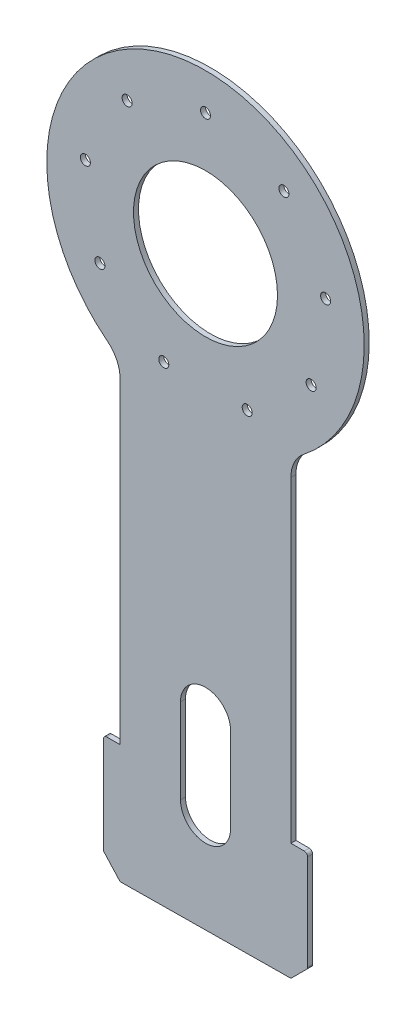
SolidWorks part; units mm, degrees
ref_plane "Front Plane" through (0, 0, 0) normal (0, 0, 1) x (1, 0, 0)
ref_plane "Top Plane" through (0, 0, 0) normal (0, 1, 0) x (1, 0, 0)
ref_plane "Right Plane" through (0, 0, 0) normal (1, 0, 0) x (0, 0, -1)
sketch "Sketch1" plane through (0, 0, 0) normal (0, 0, 1) x (1, 0, 0)
  circle A0 centre (0, 0) radius 47.5
  circle A1 centre (0, 0) radius 21.55
  dimension "D1" = 95
  dimension "D2" = 43.1
extrude "Boss-Extrude1" add sketch "Sketch1" along normal blind 1.5
sketch "Sketch2" plane through (0, 0, 1.5) normal (0, 0, 1) x (1, 0, 0)
  circle A0 centre (0, 0) radius 36.5 construction
  dimension "D1" = 73
sketch "Sketch3" plane through (0, 0, 1.5) normal (0, 0, 1) x (1, 0, 0)
  circle A0 centre (0, 36.5) radius 1.5
  circle A1 centre (0, 0) radius 36.5 construction
  point P0 (0, 36.5)
  dimension "D1" = 3
hole_wizard "Ø3.0mm Dowel Hole1" positions "Sketch3" profile "Sketch4" hole size "Ø3.0" standard "ANSI Metric" end condition through all
sketch "Sketch4" plane through (0, 36.5, 1.5) normal (1, 0, 0) x (0, -1, 0)
  line L0 (0, 0) -> (0, 1.5)
  line L1 (0, 1.5) -> (1.5, 1.5)
  line L2 (1.5, 1.5) -> (1.5, 0)
  line L5 (1.5, 0) -> (0, 0)
  line L11 (0, -6.35) -> (0, 107.95) construction
  dimension "Thru Hole Dia." = 3
  dimension "Thru Hole Depth" = 1.5
pattern_circular "CirPattern1" count 9 over 360 about axis through (0, 0, 1.5) along (0, 0, 1) of "Ø3.0mm Dowel Hole1"
sketch "Sketch6" plane through (0, 0, 1.5) normal (0, 0, 1) x (1, 0, 0)
  line L0 (0, -47.5) -> (0, -40.0345) construction
  line L1 (0, -40.0345) -> (-25.5634, -40.0345) construction
  line L2 (-25.5634, -40.0345) -> (25.5634, -40.0345) construction
  line L3 (-25.5634, -40.0345) -> (25.5634, -40.0345)
  line L4 (-25.5634, -40.0345) -> (-25.5634, -140.0345)
  line L5 (-25.5634, -140.0345) -> (-30.5634, -140.0345)
  line L6 (-30.5634, -140.0345) -> (-30.5634, -170.0345)
  line L7 (-30.5634, -170.0345) -> (-25.5634, -175.5368)
  line L8 (30.5634, -140.0345) -> (30.5634, -170.0345)
  line L9 (25.5634, -40.0345) -> (25.5634, -140.0345)
  line L10 (25.5634, -140.0345) -> (30.5634, -140.0345)
  line L11 (30.5634, -170.0345) -> (25.5634, -175.0345)
  line L12 (25.5634, -175.0345) -> (-25.5634, -175.5368)
  circle A1 centre (0, 0) radius 47.5 construction
extrude "Boss-Extrude2" add sketch "Sketch6" against normal blind 1.5
fillet "Fillet7" radius 10 1 edges at (-25.5634, -40.0345, 0.75)
fillet "Fillet8" radius 10 1 edges at (25.5634, -40.0345, 0.75)
fillet "Fillet9" radius 1 2 edges at (-30.5634, -140.0345, 0.75) (30.5634, -140.0345, 0.75)
fillet "Fillet10" radius 1 4 edges at (-30.5634, -170.0345, 0.75) (-25.5634, -175.5368, 0.75) (25.5634, -175.0345, 0.75) (30.5634, -170.0345, 0.75)
sketch "Sketch8" plane through (0, 0, 0) normal (0, 0, -1) x (-1, 0, 0)
  line L0 (-0.02, -175.2854) -> (-0.02, -145.2854) construction
  line L1 (25.1151, -175.5324) -> (-25.155, -175.0385) construction
  line L2 (-0.02, -145.2854) -> (-0.02, -119.8854) construction
  line L3 (-7.52, -145.2854) -> (-7.52, -119.8854)
  line L4 (7.48, -145.2854) -> (7.48, -119.8854)
  arc A0 (-7.52, -145.2854) -> (7.48, -145.2854) centre (-0.02, -145.2854) ccw
  arc A1 (7.48, -119.8854) -> (-7.52, -119.8854) centre (-0.02, -119.8854) ccw
  point P4 (-0.02, -132.5854)
extrude "Cut-Extrude2" cut sketch "Sketch8" against normal blind 1.5
